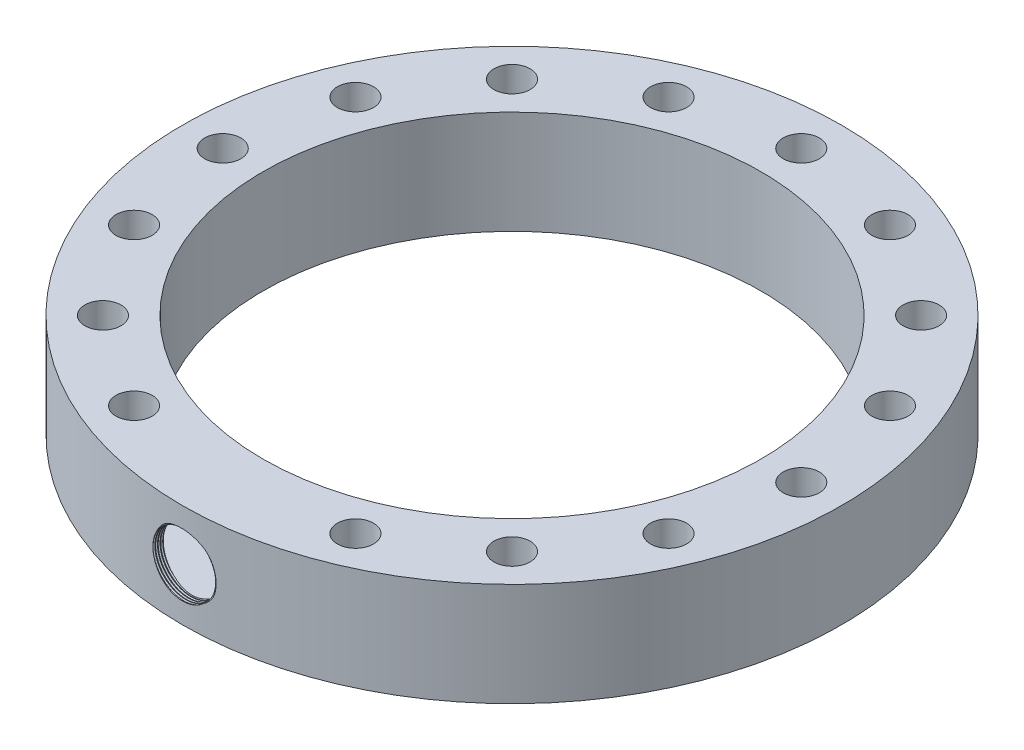
SolidWorks part; units mm, degrees
material "ABS"
ref_plane "Front Plane" through (0, 0, 0) normal (0, 0, 1) x (1, 0, 0)
ref_plane "Top Plane" through (0, 0, 0) normal (0, 1, 0) x (1, 0, 0)
ref_plane "Right Plane" through (0, 0, 0) normal (1, 0, 0) x (0, 0, -1)
sketch "Sketch2" plane through (0, 0, 0) normal (0, 1, 0) x (1, 0, 0)
  circle A0 centre (0, 0) radius 31.9
  circle A1 centre (0, 0) radius 24.1
  dimension "D1" = 63.8
  dimension "D2" = 48.2
extrude "Boss-Extrude1" add sketch "Sketch2" along normal mid plane 10
sketch "Sketch3" plane through (0, 0, 0) normal (0, 0, 1) x (1, 0, 0)
  line L0 (24.1, 5) -> (-24.1, 5) construction
  circle A0 centre (0, 0) radius 3
  dimension "D1" = 6
  dimension "D2" = 5
extrude "Cut-Extrude1" cut sketch "Sketch3" along normal blind 40 from offset 27
sketch "Sketch4" plane through (0, 0, 0) normal (1, 0, 0) x (0, 0, -1)
  line L0 (0, -1000) -> (0, 49000) construction
  line L2 (-30.9005, 4) -> (-25.2995, 4)
  line L3 (-30.9005, 4) -> (-30.9005, -4)
  line L4 (-30.9005, -4) -> (-25.2995, -4)
  line L5 (-25.2995, 4) -> (-25.2995, -4)
  line L6 (-30.9005, 4) -> (-25.2995, -4) construction
  line L7 (-30.9005, -4) -> (-25.2995, 4) construction
  point P0 (-24.1, 5)
  point P1 (-28.1, 0)
  point P9 (-31.9, 5)
  dimension "D2" = 1
  dimension "D1" = 8
  dimension "D3" = 5.6009
  dimension "D4" = 1.1995
  dimension "D5" = 0.9995
revolve "Cut-Revolve1" cut sketch "Sketch4" angle 360 about L0 other way angle 360
ref_plane "Plane1" through (0, 0, 32) normal (0, 0, 1) x (1, 0, 0)
thread "Thread1" pitch 0.25 method cut profile "Thread Profile1" start angle 0, offset 0, length 3, pitch 0.25, diameter 6
ref_plane "Plane2" through (-3, 0, 32) normal (0, -1, 0) x (-1, 0, 0)
sketch "Thread Profile1" plane through (-3, 0, 32) normal (0, -1, 0) x (-1, 0, 0)
  line L0 (0, 0) -> (0, 0.25) construction
  line L1 (0, 0) -> (0.1353, 0.0781)
  line L2 (0.1353, 0.0781) -> (0.1353, 0.1094)
  line L3 (0.1353, 0.1094) -> (0, 0.1875)
  line L4 (0.1353, 0.0937) -> (0, 0.0937) construction
  line L11 (0, 0) -> (0, 0.1875)
  point P2 (0, 0)
  dimension "Pitch" = 0.25
  dimension "Profile_Angle" = 60
  dimension "Profile_Land" = 0.0312
  dimension "Profile_Height" = 0.1353
sketch "Sketch5" plane through (0, 5, 0) normal (0, 1, 0) x (1, 0, 0)
  circle A0 centre (0, 28) radius 2.25
  circle A1 centre (0, 28) radius 1.75
  circle A2 centre (10.7151, 25.8686) radius 1.75
  circle A3 centre (10.7151, 25.8686) radius 2.25
  circle A4 centre (19.799, 19.799) radius 1.75
  circle A5 centre (19.799, 19.799) radius 2.25
  circle A6 centre (25.8686, 10.7151) radius 1.75
  circle A7 centre (25.8686, 10.7151) radius 2.25
  circle A8 centre (28, 0) radius 1.75
  circle A9 centre (28, 0) radius 2.25
  circle A10 centre (25.8686, -10.7151) radius 1.75
  circle A11 centre (25.8686, -10.7151) radius 2.25
  circle A12 centre (19.799, -19.799) radius 1.75
  circle A13 centre (19.799, -19.799) radius 2.25
  circle A14 centre (10.7151, -25.8686) radius 1.75
  circle A15 centre (10.7151, -25.8686) radius 2.25
  circle A18 centre (-10.7151, -25.8686) radius 1.75
  circle A19 centre (-10.7151, -25.8686) radius 2.25
  circle A20 centre (-19.799, -19.799) radius 1.75
  circle A21 centre (-19.799, -19.799) radius 2.25
  circle A22 centre (-25.8686, -10.7151) radius 1.75
  circle A23 centre (-25.8686, -10.7151) radius 2.25
  circle A24 centre (-28, 0) radius 1.75
  circle A25 centre (-28, 0) radius 2.25
  circle A26 centre (-25.8686, 10.7151) radius 1.75
  circle A27 centre (-25.8686, 10.7151) radius 2.25
  circle A28 centre (-19.799, 19.799) radius 1.75
  circle A29 centre (-19.799, 19.799) radius 2.25
  circle A30 centre (-10.7151, 25.8686) radius 1.75
  circle A31 centre (-10.7151, 25.8686) radius 2.25
  circle A32 centre (0, -28) radius 2.25 [skipped]
  circle A33 centre (0, -28) radius 1.75 [skipped]
  point P51 (0, 0)
  dimension "D1" = 4.5
  dimension "D2" = 3.5
  dimension "D3" = 28
  dimension "D4" = 16
extrude "Boss-Extrude2" add sketch "Sketch5" against normal blind 10
sketch "Sketch7" plane through (0, 0, 0) normal (1, 0, 0) x (0, 0, -1)
  line L0 (0, -1000) -> (0, 49000) construction
  circle A0 centre (-28.1017, 0) radius 0.5
  dimension "D1" = 1
revolve "Cut-Revolve2" cut sketch "Sketch7" angle 360 about L0
sketch "Sketch8" plane through (0, 5, 0) normal (0, 1, 0) x (1, 0, 0)
  circle A0 centre (0, 28) radius 1.75
  circle A1 centre (10.7151, 25.8686) radius 1.75
  circle A2 centre (19.799, 19.799) radius 1.75
  circle A3 centre (25.8686, 10.7151) radius 1.75
  circle A4 centre (28, 0) radius 1.75
  circle A5 centre (25.8686, -10.7151) radius 1.75
  circle A6 centre (19.799, -19.799) radius 1.75
  circle A7 centre (10.7151, -25.8686) radius 1.75
  circle A9 centre (-10.7151, -25.8686) radius 1.75
  circle A10 centre (-19.799, -19.799) radius 1.75
  circle A11 centre (-25.8686, -10.7151) radius 1.75
  circle A12 centre (-28, 0) radius 1.75
  circle A13 centre (-25.8686, 10.7151) radius 1.75
  circle A14 centre (-19.799, 19.799) radius 1.75
  circle A15 centre (-10.7151, 25.8686) radius 1.75
  circle A16 centre (0, -28) radius 1.75 [skipped]
  point P35 (0, 0)
  dimension "D1" = 3.5
  dimension "D2" = 28
  dimension "D3" = 16
extrude "Cut-Extrude2" cut sketch "Sketch8" against normal through all
